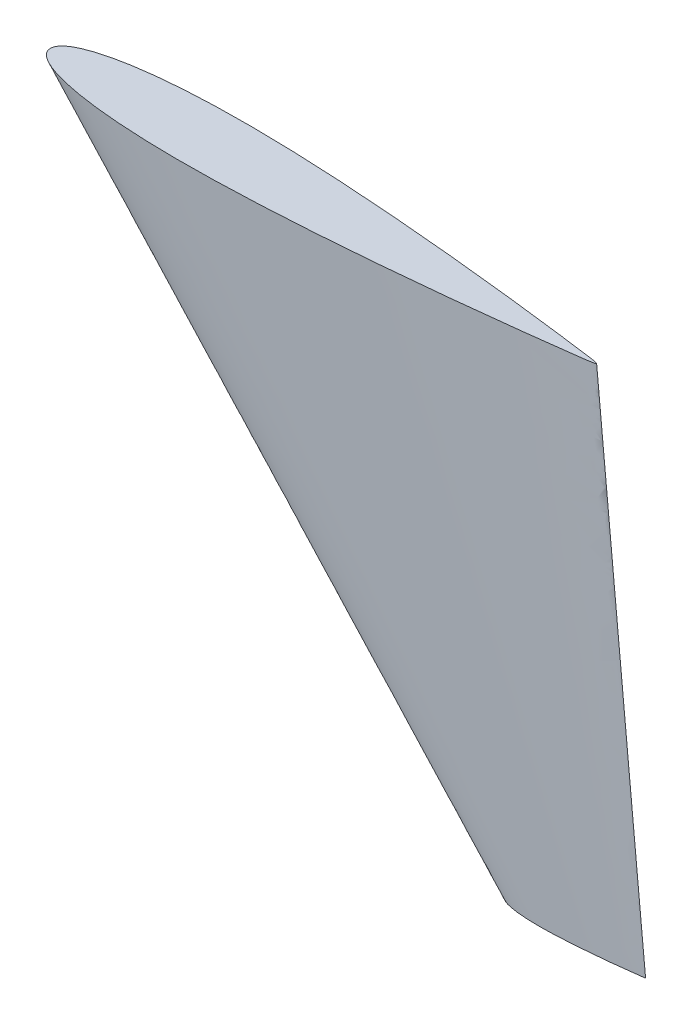
SolidWorks part; units mm, degrees
ref_plane "Front Plane" through (0, 0, 0) normal (0, 0, 1) x (1, 0, 0)
ref_plane "Top Plane" through (0, 0, 0) normal (0, 1, 0) x (1, 0, 0)
ref_plane "Right Plane" through (0, 0, 0) normal (1, 0, 0) x (0, 0, -1)
curve "Curve1"
  spline degree 3 poles (989.1889, 0, -3.124) (1003.9656, 0, 0) (989.1889, 0, 3.124) (979.4957, 0, 3.9602) (962.3964, 0, 6.4841) (943.9428, 0, 8.8491) (922.9132, 0, 11.6051) (900.2887, 0, 14.4478) (876.1894, 0, 17.4113) (850.9063, 0, 20.4351) (824.6249, 0, 23.4743) (797.5193, 0, 26.5234) (769.735, 0, 29.5334) (741.4059, 0, 32.5134) (712.6526, 0, 35.4198) (683.5857, 0, 38.2366) (654.3085, 0, 40.9505) (624.9168, 0, 43.5692) (595.4919, 0, 46.0176) (566.1196, 0, 48.3457) (536.8752, 0, 50.4873) (507.8364, 0, 52.4785) (479.0688, 0, 54.2437) (450.6418, 0, 55.8057) (422.6181, 0, 57.149) (395.0577, 0, 58.2561) (368.0197, 0, 59.0905) (341.5624, 0, 59.6944) (315.7376, 0, 59.999) (290.5993, 0, 60.0553) (266.1976, 0, 59.7899) (242.5818, 0, 59.2641) (219.7995, 0, 58.4267) (197.8965, 0, 57.3046) (176.9228, 0, 55.8955) (156.9193, 0, 54.1908) (137.9264, 0, 52.2182) (119.9888, 0, 49.9445) (103.1457, 0, 47.4173) (87.4377, 0, 44.6503) (72.9094, 0, 41.6113) (59.5881, 0, 38.3545) (47.5124, 0, 34.8789) (36.7185, 0, 31.1996) (27.2445, 0, 27.3184) (19.1092, 0, 23.264) (12.343, 0, 19.027) (6.9689, 0, 14.6049) (3.0199, 0, 9.972) (0.5665, 0, 5.0849) (-0.2745, 0, 0) (0.5665, 0, -5.0849) (3.0199, 0, -9.972) (6.9689, 0, -14.6049) (12.343, 0, -19.027) (19.1092, 0, -23.264) (27.2445, 0, -27.3184) (36.7185, 0, -31.1996) (47.5124, 0, -34.8789) (59.5881, 0, -38.3545) (72.9094, 0, -41.6113) (87.4377, 0, -44.6503) (103.1457, 0, -47.4173) (119.9888, 0, -49.9445) (137.9264, 0, -52.2182) (156.9193, 0, -54.1908) (176.9228, 0, -55.8955) (197.8965, 0, -57.3046) (219.7995, 0, -58.4267) (242.5818, 0, -59.2641) (266.1976, 0, -59.7899) (290.5993, 0, -60.0553) (315.7376, 0, -59.999) (341.5624, 0, -59.6944) (368.0197, 0, -59.0905) (395.0577, 0, -58.2561) (422.6181, 0, -57.149) (450.6418, 0, -55.8057) (479.0688, 0, -54.2437) (507.8364, 0, -52.4785) (536.8752, 0, -50.4873) (566.1196, 0, -48.3457) (595.4919, 0, -46.0176) (624.9168, 0, -43.5692) (654.3085, 0, -40.9505) (683.5857, 0, -38.2366) (712.6526, 0, -35.4198) (741.4059, 0, -32.5134) (769.735, 0, -29.5334) (797.5193, 0, -26.5234) (824.6249, 0, -23.4743) (850.9063, 0, -20.4351) (876.1894, 0, -17.4113) (900.2887, 0, -14.4478) (922.9132, 0, -11.6051) (943.9428, 0, -8.8491) (962.3964, 0, -6.4841) (979.4957, 0, -3.9602) (989.1889, 0, -3.124) (1003.9656, 0, 0) (989.1889, 0, 3.124) knots -0.01819 -0.010091 -0.003701 0 0.003701 0.010091 0.01819 0.027571 0.037978 0.04922 0.061159 0.073676 0.086676 0.10007 0.113795 0.12778 0.141967 0.156301 0.170733 0.185213 0.199702 0.214161 0.22855 0.24283 0.256971 0.270941 0.284704 0.298236 0.311509 0.32449 0.337159 0.349495 0.361463 0.373051 0.384237 0.394993 0.405307 0.415153 0.424519 0.43339 0.441745 0.449568 0.456846 0.463572 0.469733 0.475323 0.480337 0.484781 0.488676 0.492055 0.49498 0.497567 0.5 0.502433 0.50502 0.507945 0.511324 0.515219 0.519663 0.524677 0.530267 0.536428 0.543154 0.550432 0.558255 0.56661 0.575481 0.584847 0.594693 0.605007 0.615763 0.626949 0.638537 0.650505 0.662841 0.67551 0.688491 0.701764 0.715296 0.729059 0.743029 0.75717 0.77145 0.785839 0.800298 0.814787 0.829267 0.843699 0.858033 0.87222 0.886205 0.89993 0.913324 0.926324 0.938841 0.95078 0.962022 0.972429 0.98181 0.989909 0.996299 1 1.003701 1.010091 1.01819 periodic
sketch "Sketch2" plane through (0, 0, 0) normal (0, 1, 0) x (1, 0, 0)
  line L0 (7800, 0) -> (0, 0) construction
  line L1 (0, 0) -> (0, 395.0757) construction
  spline S1 degree 3 poles (7715.6733, -24.367) (7830.9313, 0) (7715.6733, 24.367) (7640.0665, 30.8898) (7506.6921, 50.5762) (7362.7536, 69.0228) (7198.7231, 90.52) (7022.252, 112.6929) (6834.2776, 135.808) (6637.0694, 159.3941) (6432.074, 183.0993) (6220.6504, 206.8827) (6003.9328, 230.3604) (5782.9657, 253.6049) (5558.6901, 276.2741) (5331.9683, 298.2455) (5103.6066, 319.4138) (4874.3512, 339.8394) (4644.8367, 358.9371) (4415.733, 377.0965) (4187.6269, 393.8012) (3961.1239, 409.3322) (3736.7364, 423.1006) (3515.0057, 435.2847) (3296.4215, 445.7625) (3081.4499, 454.3974) (2870.5539, 460.9058) (2664.1865, 465.6165) (2462.7531, 467.9925) (2266.6747, 468.431) (2076.3415, 466.3609) (1892.1383, 462.2603) (1714.4358, 455.7279) (1543.593, 446.9762) (1379.9976, 435.9846) (1223.9703, 422.6886) (1075.8258, 407.3018) (935.9126, 389.5669) (804.5364, 369.855) (682.0138, 348.2726) (568.693, 324.5681) (464.7869, 299.1653) (370.5968, 272.0553) (286.404, 243.3569) (212.5068, 213.0831) (149.052, 181.4593) (96.2758, 148.4109) (54.3577, 113.9185) (23.5554, 77.7814) (4.4187, 39.662) (-2.1412, 0) (4.4187, -39.662) (23.5554, -77.7814) (54.3577, -113.9185) (96.2758, -148.4109) (149.052, -181.4593) (212.5068, -213.0831) (286.404, -243.3569) (370.5968, -272.0553) (464.7869, -299.1653) (568.693, -324.5681) (682.0138, -348.2726) (804.5364, -369.855) (935.9126, -389.5669) (1075.8258, -407.3018) (1223.9703, -422.6886) (1379.9976, -435.9846) (1543.593, -446.9762) (1714.4358, -455.7279) (1892.1383, -462.2603) (2076.3415, -466.3609) (2266.6747, -468.431) (2462.7531, -467.9925) (2664.1865, -465.6165) (2870.5539, -460.9058) (3081.4499, -454.3974) (3296.4215, -445.7625) (3515.0057, -435.2847) (3736.7364, -423.1006) (3961.1239, -409.3322) (4187.6269, -393.8012) (4415.733, -377.0965) (4644.8367, -358.9371) (4874.3512, -339.8394) (5103.6066, -319.4138) (5331.9683, -298.2455) (5558.6901, -276.2741) (5782.9657, -253.6049) (6003.9328, -230.3604) (6220.6504, -206.8827) (6432.074, -183.0993) (6637.0694, -159.3941) (6834.2776, -135.808) (7022.252, -112.6929) (7198.7231, -90.52) (7362.7536, -69.0228) (7506.6921, -50.5762) (7640.0665, -30.8898) (7715.6733, -24.367) (7830.9313, 0) (7715.6733, 24.367) knots -0.01819 -0.010091 -0.003701 0 0.003701 0.010091 0.01819 0.027571 0.037978 0.04922 0.061159 0.073676 0.086676 0.10007 0.113795 0.12778 0.141967 0.156301 0.170733 0.185213 0.199702 0.214161 0.22855 0.24283 0.256971 0.270941 0.284704 0.298236 0.311509 0.32449 0.337159 0.349495 0.361463 0.373051 0.384237 0.394993 0.405307 0.415153 0.424519 0.43339 0.441745 0.449568 0.456846 0.463572 0.469733 0.475323 0.480337 0.484781 0.488676 0.492055 0.49498 0.497567 0.5 0.502433 0.50502 0.507945 0.511324 0.515219 0.519663 0.524677 0.530267 0.536428 0.543154 0.550432 0.558255 0.56661 0.575481 0.584847 0.594693 0.605007 0.615763 0.626949 0.638537 0.650505 0.662841 0.67551 0.688491 0.701764 0.715296 0.729059 0.743029 0.75717 0.77145 0.785839 0.800298 0.814787 0.829267 0.843699 0.858033 0.87222 0.886205 0.89993 0.913324 0.926324 0.938841 0.95078 0.962022 0.972429 0.98181 0.989909 0.996299 1 1.003701 1.010091 1.01819 only from (7800, 0) to (7800, 0)
  dimension "D1" = 7800
ref_plane "Plane1" through (0, -7250, 0) normal (0, 1, 0) x (1, 0, 0)
sketch "Sketch6" plane through (0, -7250, 0) normal (0, 1, 0) x (1, 0, 0)
  line L0 (8500, 0) -> (6500, 0) construction
  line L1 (6500, 0) -> (6500, 213.2137) construction
  line L2 (7800, 0) -> (0, 0) construction
  spline S1 degree 3 poles (8478.3778, -6.2479) (8507.9311, 0) (8478.3778, 6.2479) (8458.9914, 7.9205) (8424.7929, 12.9683) (8387.8855, 17.6982) (8345.8264, 23.2103) (8300.5774, 28.8956) (8252.3789, 34.8226) (8201.8127, 40.8703) (8149.2497, 46.9485) (8095.0386, 53.0469) (8039.4699, 59.0668) (7982.8117, 65.0269) (7925.3052, 70.8395) (7867.1714, 76.4732) (7808.6171, 81.901) (7749.8336, 87.1383) (7690.9838, 92.0352) (7632.2392, 96.6914) (7573.7505, 100.9747) (7515.6728, 104.957) (7458.1376, 108.4873) (7401.2835, 111.6115) (7345.2363, 114.2981) (7290.1154, 116.5121) (7236.0395, 118.181) (7183.1248, 119.3888) (7131.4752, 119.9981) (7081.1987, 120.1105) (7032.3952, 119.5797) (6985.1637, 118.5283) (6939.5989, 116.8533) (6895.7931, 114.6093) (6853.8455, 111.7909) (6813.8385, 108.3817) (6775.8528, 104.4364) (6739.9776, 99.889) (6706.2914, 94.8346) (6674.8753, 89.3007) (6645.8187, 83.2226) (6619.1761, 76.709) (6595.0248, 69.7578) (6573.4369, 62.3992) (6554.4889, 54.6367) (6538.2185, 46.528) (6524.6861, 38.0541) (6513.9379, 29.2099) (6506.0399, 19.9439) (6501.133, 10.1697) (6499.451, 0) (6501.133, -10.1697) (6506.0399, -19.9439) (6513.9379, -29.2099) (6524.6861, -38.0541) (6538.2185, -46.528) (6554.4889, -54.6367) (6573.4369, -62.3992) (6595.0248, -69.7578) (6619.1761, -76.709) (6645.8187, -83.2226) (6674.8753, -89.3007) (6706.2914, -94.8346) (6739.9776, -99.889) (6775.8528, -104.4364) (6813.8385, -108.3817) (6853.8455, -111.7909) (6895.7931, -114.6093) (6939.5989, -116.8533) (6985.1637, -118.5283) (7032.3952, -119.5797) (7081.1987, -120.1105) (7131.4752, -119.9981) (7183.1248, -119.3888) (7236.0395, -118.181) (7290.1154, -116.5121) (7345.2363, -114.2981) (7401.2835, -111.6115) (7458.1376, -108.4873) (7515.6728, -104.957) (7573.7505, -100.9747) (7632.2392, -96.6914) (7690.9838, -92.0352) (7749.8336, -87.1383) (7808.6171, -81.901) (7867.1714, -76.4732) (7925.3052, -70.8395) (7982.8117, -65.0269) (8039.4699, -59.0668) (8095.0386, -53.0469) (8149.2497, -46.9485) (8201.8127, -40.8703) (8252.3789, -34.8226) (8300.5774, -28.8956) (8345.8264, -23.2103) (8387.8855, -17.6982) (8424.7929, -12.9683) (8458.9914, -7.9205) (8478.3778, -6.2479) (8507.9311, 0) (8478.3778, 6.2479) knots -0.01819 -0.010091 -0.003701 0 0.003701 0.010091 0.01819 0.027571 0.037978 0.04922 0.061159 0.073676 0.086676 0.10007 0.113795 0.12778 0.141967 0.156301 0.170733 0.185213 0.199702 0.214161 0.22855 0.24283 0.256971 0.270941 0.284704 0.298236 0.311509 0.32449 0.337159 0.349495 0.361463 0.373051 0.384237 0.394993 0.405307 0.415153 0.424519 0.43339 0.441745 0.449568 0.456846 0.463572 0.469733 0.475323 0.480337 0.484781 0.488676 0.492055 0.49498 0.497567 0.5 0.502433 0.50502 0.507945 0.511324 0.515219 0.519663 0.524677 0.530267 0.536428 0.543154 0.550432 0.558255 0.56661 0.575481 0.584847 0.594693 0.605007 0.615763 0.626949 0.638537 0.650505 0.662841 0.67551 0.688491 0.701764 0.715296 0.729059 0.743029 0.75717 0.77145 0.785839 0.800298 0.814787 0.829267 0.843699 0.858033 0.87222 0.886205 0.89993 0.913324 0.926324 0.938841 0.95078 0.962022 0.972429 0.98181 0.989909 0.996299 1 1.003701 1.010091 1.01819 only from (8500, 0) to (8500, 0)
  point P1 (6500, 0)
  dimension "D1" = 2000
  dimension "D2" = 6500
loft "Loft2" add profiles "Sketch6", "Sketch2" connector at (8499.9828, -7250, -0.1359) connector at (7799.7348, 0, -1.0598)
